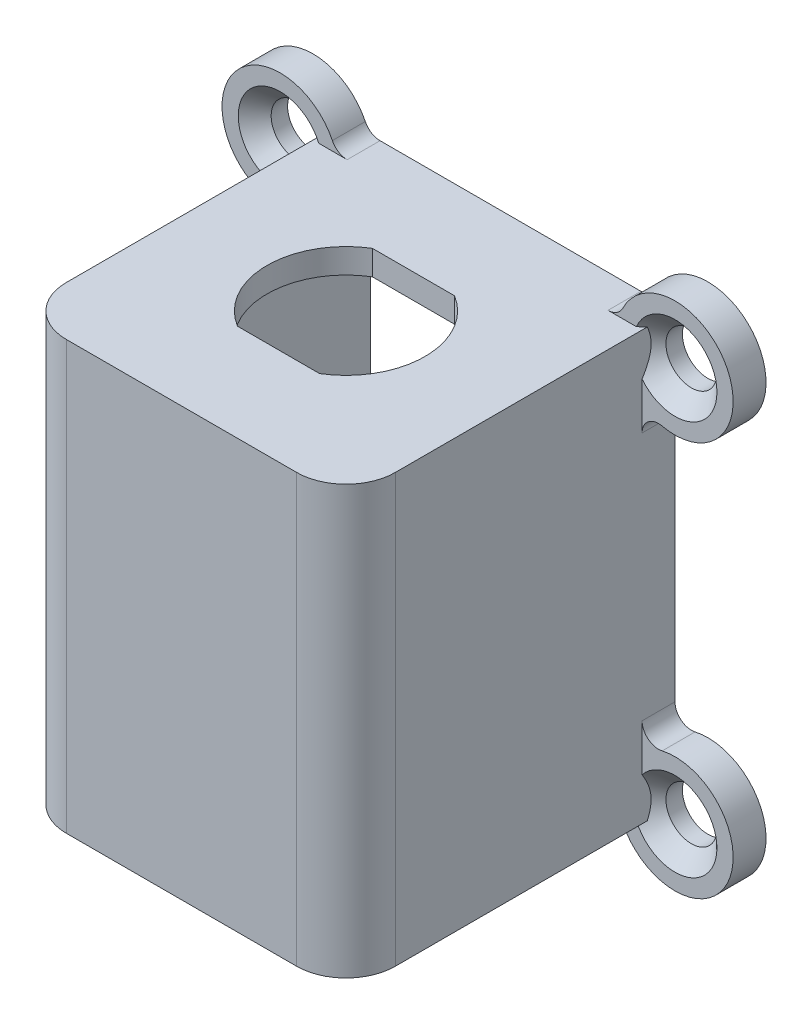
SolidWorks part; units mm, degrees
ref_plane "Спереди" through (0, 0, 0) normal (0, 0, 1) x (1, 0, 0)
ref_plane "Сверху" through (0, 0, 0) normal (0, 1, 0) x (1, 0, 0)
ref_plane "Справа" through (0, 0, 0) normal (1, 0, 0) x (0, 0, -1)
sketch "Эскиз1" plane through (0, 0, 0) normal (0, 1, 0) x (1, 0, 0)
  line L2 (-10, 10) -> (10, 10)
  line L4 (-10, 10) -> (-10, -7)
  line L7 (-7, -10) -> (7, -10)
  line L8 (10, 10) -> (10, -7)
  line L9 (-10, 10) -> (10, -10) construction
  line L10 (-10, -10) -> (10, 10) construction
  arc A2 (7, -10) -> (10, -7) centre (7, -7) ccw
  arc A3 (-10, -7) -> (-7, -10) centre (-7, -7) ccw
  dimension "D5" = 3
  dimension "D3" = 20
  dimension "D4" = 20
extrude "Бобышка-Вытянуть1" add sketch "Эскиз1" along normal blind 26
shell "Оболочка2" thickness 1.5 removed face at (0, 13, -10)
sketch "Эскиз3" plane through (0, 26, 0) normal (0, 1, 0) x (1, 0, 0)
  line L0 (0, 10) -> (0, -10) construction
  line L1 (10, 10) -> (-10, 10) construction
  line L2 (-7, -10) -> (7, -10) construction
  line L4 (2.496, 4.1) -> (-2.496, 4.1)
  line L6 (2.496, -4.1) -> (-2.496, -4.1)
  line L8 (2.496, 4.1) -> (-2.496, -4.1) construction
  line L9 (2.496, -4.1) -> (-2.496, 4.1) construction
  arc A0 (-2.496, 4.1) -> (-2.496, -4.1) centre (0, 0) ccw
  arc A1 (2.496, -4.1) -> (2.496, 4.1) centre (0, 0) ccw
  dimension "D1" = 9.6
  dimension "D2" = 8.2
extrude "Вырез-Вытянуть1" cut sketch "Эскиз3" against normal up to next
sketch "Эскиз4" plane through (0, 0, -10) normal (0, 0, -1) x (-1, 0, 0)
  line L0 (0, 26) -> (0, 0) construction
  line L1 (-10, 26) -> (10, 26) construction
  line L2 (-10, 0) -> (10, 0) construction
  line L3 (-10, 13) -> (10, 13) construction
  line L4 (-10, 26) -> (-10, 0) construction
  line L5 (10, 26) -> (10, 0) construction
  line L7 (12, 1) -> (-12, 1) construction
  line L8 (12, 1) -> (12, 25) construction
  line L9 (12, 25) -> (-12, 25) construction
  line L10 (-12, 1) -> (-12, 25) construction
  line L11 (12, 1) -> (-12, 25) construction
  line L12 (12, 25) -> (-12, 1) construction
  circle A0 centre (12, 25) radius 1.55
  circle A1 centre (12, 25) radius 3.5355
  circle A2 centre (-12, 25) radius 1.55
  circle A3 centre (-12, 25) radius 3.5355
  circle A4 centre (12, 1) radius 1.55
  circle A5 centre (12, 1) radius 3.5355
  circle A6 centre (-12, 1) radius 3.5355
  circle A7 centre (-12, 1) radius 1.55
  point P12 (0, 13)
  dimension "D3" = 3.1
  dimension "D1" = 2
  dimension "D2" = 24
extrude "Бобышка-Вытянуть3" add sketch "Эскиз4" against normal blind 2
chamfer "Фаска1" distance 1 angle 45 4 edges at (13.55, 25, -8) (10.45, 1, -8) (-10.45, 1, -8) (-13.55, 25, -8)
fillet "Скругление1" radius 1 8 edges at (-10, 3.9155, -9) (-10, 22.0845, -9) (-8.6088, 26, -9) (8.6088, 26, -9) (-8.6088, 0, -9) (8.6088, 0, -9) (10, 22.0845, -9) (10, 3.9155, -9)
